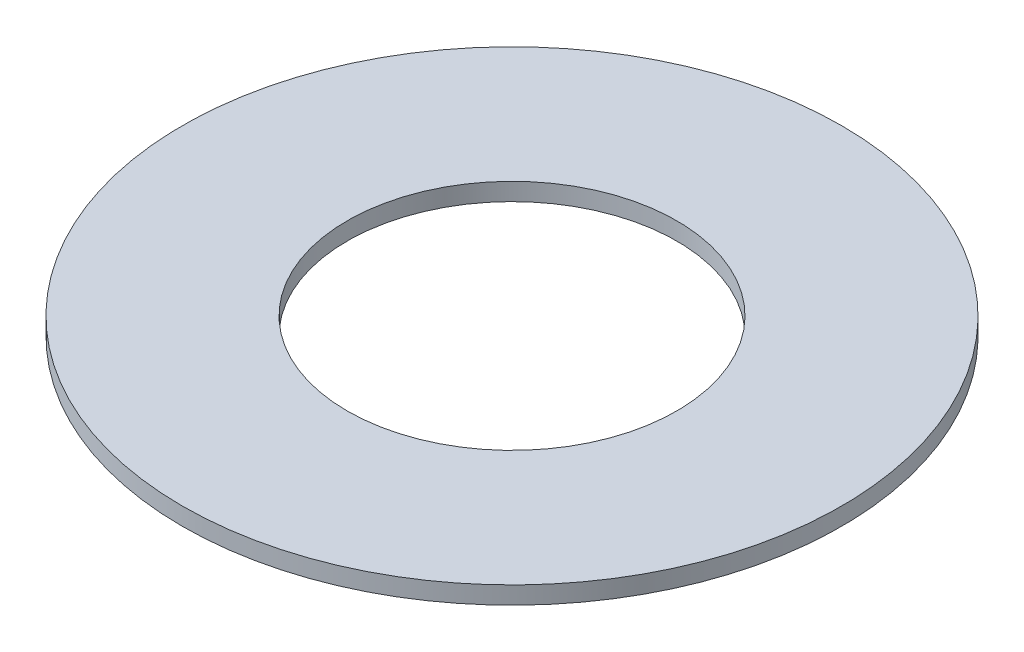
SolidWorks part; units mm, degrees
ref_plane "Front Plane" through (0, 0, 0) normal (0, 0, 1) x (1, 0, 0)
ref_plane "Top Plane" through (0, 0, 0) normal (0, 1, 0) x (1, 0, 0)
ref_plane "Right Plane" through (0, 0, 0) normal (1, 0, 0) x (0, 0, -1)
sketch "Sketch1" plane through (0, 0, 0) normal (0, 1, 0) x (1, 0, 0)
  circle A0 centre (0, 0) radius 75
  dimension "FLANGE_OD" = 150
extrude "Boss-Extrude1" add sketch "Sketch1" along normal blind 4
sketch "Sketch2" plane through (0, 0, 0) normal (0, 1, 0) x (1, 0, 0)
  circle A0 centre (0, 0) radius 37.5
  dimension "BORE_D" = 75
extrude "Cut-Extrude1" cut sketch "Sketch2" along normal through all
sketch "Sketch3" plane through (0, 4, 0) normal (0, 1, 0) x (1, 0, 0)
  circle A0 centre (0, 0) radius 25.7547 construction
  circle A1 centre (-25.7547, 0) radius 6.2795
  dimension "BOLT_D" = 12.559
  dimension "BOLT_PCD" = 51.5094
extrude "Cut-Extrude2" cut sketch "Sketch3" against normal blind 3.6715 rebuild error yes
pattern_circular "CirPattern1" count 6 over 360 rebuild error yes
